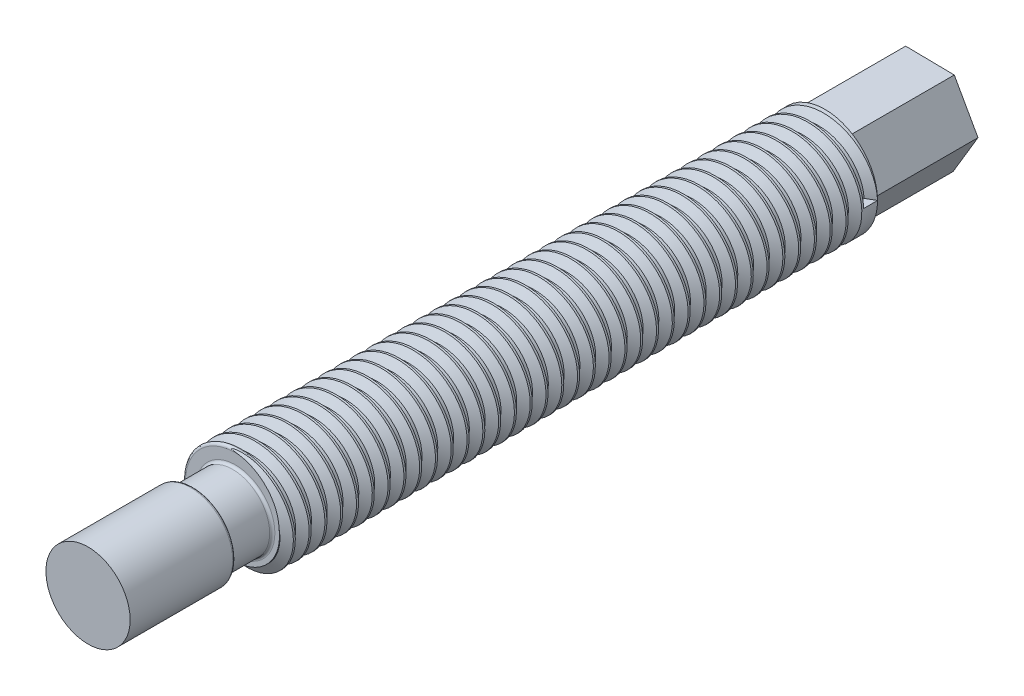
SolidWorks part; units mm, degrees
note: '?' marks a value the reader was unsure of.
ref_plane "Front Plane" through (0, 0, 0) normal (0, 0, 1) x (1, 0, 0)
ref_plane "Top Plane" through (0, 0, 0) normal (0, 1, 0) x (1, 0, 0)
ref_plane "Right Plane" through (0, 0, 0) normal (1, 0, 0) x (0, 0, -1)
sketch "Sketch1" plane through (0, 0, 0) normal (0, 0, 1) x (1, 0, 0)
  circle A0 centre (0, 0) radius 5
  dimension "D1" = 10
extrude "Boss-Extrude1" add sketch "Sketch1" along normal blind 80
sketch "Sketch4" plane through (0, 0, 80) normal (0, 0, 1) x (1, 0, 0)
  circle A0 centre (0, 0) radius 4
  circle A2 centre (0, 0) radius 5
  dimension "D1" = 8
extrude "Cut-Extrude1" cut sketch "Sketch4" against normal blind 10
sketch "Sketch5" plane through (0, 0, 70) normal (0, 0, 1) x (1, 0, 0)
  circle A0 centre (0, 0) radius 3.5
  circle A1 centre (0, 0) radius 5
  dimension "D1" = 7
extrude "Cut-Extrude2" cut sketch "Sketch5" against normal blind 4
fillet "Fillet1" radius 0.25 4 edges at (3.5, 0, 66) (3.5, 0, 70) (4, 0, 70) (5, 0, 66)
ref_axis "Axis1" through (0, 0, 70.25) along (0, 0, 1)?
sketch "Sketch8" plane through (0, 0, 0) normal (1, 0, 0) x (0, 0, -1)
  line L0 (-80, 4) -> (-80, -4) construction
  line L1 (-80, 4) -> (-80, 55.0495)
  line L3 (-70.25, 4) -> (-80, 4) construction
  line L4 (-98.5805, 4) -> (-80, 4)
  line L5 (-98.5805, 4) -> (-80, 55.0495)
  point P6 (0, 0)
  dimension "D1" = 20
revolve "Cut-Revolve4" [suppressed] cut sketch "Sketch8" angle 360 about axis through (0, 0, 70.25) along (0, 0, 1)
sketch "Sketch9" plane through (0, 0, 0) normal (0, 0, -1) x (-1, 0, 0)
  line L1 (2.3312, 4.0318) -> (-2.2871, 3.9674)
  line L2 (-2.2871, 3.9674) -> (-4.5406, -0.0643)
  line L3 (-4.5406, -0.0643) -> (-2.1757, -4.0318)
  line L4 (-2.1757, -4.0318) -> (2.4427, -3.9674)
  line L5 (2.4427, -3.9674) -> (4.6961, 0.0643)
  line L6 (4.6961, 0.0643) -> (2.3312, 4.0318)
  circle A1 centre (0, 0) radius 5
extrude "Cut-Extrude3" cut sketch "Sketch9" against normal blind 10
thread "Thread1" pitch 1.5 profile "Thread Profile2" start angle 0, offset 0, length 0, pitch 1.5, diameter 10
ref_plane "Plane2" through (5, 0, 10) normal (0, -1, 0) x (1, 0, 0)
sketch "Thread Profile2" plane through (5, 0, 10) normal (0, -1, 0) x (1, 0, 0)
  line L0 (0, 0) -> (0, 1.5) construction
  line L11 (0, 0) -> (0, 1.3125)
  line L12 (0, 1.3125) -> (-0.8119, 0.8437)
  line L13 (-0.8119, 0.8437) -> (-0.8119, 0.4687)
  line L15 (-0.8119, 0.4687) -> (0, 0)
  line L17 (-0.8119, 0.6562) -> (0, 0.6562) construction
  point P2 (0, 0)
  dimension "Pitch" = 1.5
  dimension "Profile_Angle" = 60
  dimension "Profile_Land" = 0.375
  dimension "Profile_Height" = 0.8119
